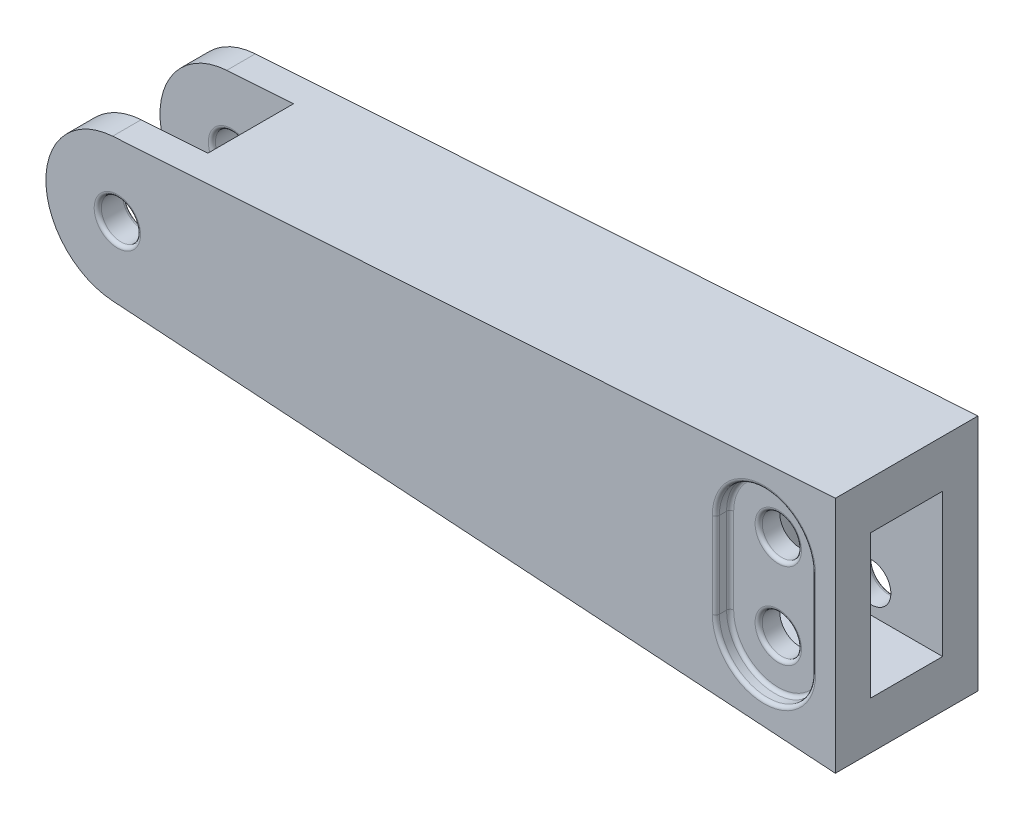
SolidWorks part; units mm, degrees
ref_plane "Front Plane" through (0, 0, 0) normal (0, 0, 1) x (1, 0, 0)
ref_plane "Top Plane" through (0, 0, 0) normal (0, 1, 0) x (1, 0, 0)
ref_plane "Right Plane" through (0, 0, 0) normal (1, 0, 0) x (0, 0, -1)
sketch "Sketch1" plane through (0, 0, 0) normal (0, 0, 1) x (1, 0, 0)
  line L0 (-50, 16.6955) -> (-151.3109, 10)
  line L1 (43.0973, 0) -> (50043.0973, 0) construction
  line L2 (0, 21.9801) -> (0, 50021.9801) construction
  line L3 (-50, -16.6955) -> (-151.3109, -10)
  line L4 (-50, 16.6955) -> (-50, -16.6955)
  line L5 (-50, 16.6955) -> (-50, -16.6955) construction
  line L6 (-6.5945, 19.5642) -> (-50, 16.6955) construction
  line L7 (-120.65, 205.549) -> (-120.65, -129.451) construction
  arc A0 (-151.3109, 10) -> (-151.3109, -10) centre (-150.65, 0) ccw
  point P9 (0, 0)
  dimension "D1" = 30
extrude "Boss-Extrude1" add sketch "Sketch1" along normal up to surface (20 mm away) contours L0 A0 L3 L4 region at (-99.4054, 0, 0)
sketch "Sketch2" plane through (-50, 0, 0) normal (1, 0, 0) x (0, 0, -1)
  line L1 (-4.965, -10.035) -> (-15.035, -10.035)
  line L2 (-4.965, -10.035) -> (-4.965, 10.035)
  line L3 (-4.965, 10.035) -> (-15.035, 10.035)
  line L4 (-20, 16.6955) -> (-20, -16.6955)
  line L5 (-20, -16.6955) -> (0, -16.6955)
  line L6 (0, -16.6955) -> (0, 16.6955)
  line L7 (0, 16.6955) -> (-20, 16.6955)
  line L8 (-20, 16.6955) -> (-20, -16.6955) construction
  line L9 (-20, -16.6955) -> (0, -16.6955) construction
  line L10 (0, -16.6955) -> (0, 16.6955) construction
  line L11 (0, 16.6955) -> (-20, 16.6955) construction
  line L12 (-15.035, -10.035) -> (-15.035, 10.035)
  line L13 (-4.965, -10.035) -> (-15.035, 10.035) construction
  line L14 (-4.965, 10.035) -> (-15.035, -10.035) construction
  point P2 (-10, 0)
  point P8 (-10, -16.6955)
  point P9 (-10, 0)
  dimension "D2" = 20.07
  dimension "D3" = 10.07
  dimension "D1" = 0
extrude "Cut-Extrude1" cut sketch "Sketch2" against normal blind 20
sketch "Sketch4" plane through (0, 0, 0) normal (0, 1, 0) x (1, 0, 0)
  line L0 (-160.6718, 0) -> (-160.6718, -20) construction
  line L1 (-160.6718, -4) -> (-141.95, -4)
  line L2 (-160.6718, -4) -> (-160.6718, -16)
  line L3 (-160.6718, -16) -> (-141.95, -16)
  line L4 (-141.95, -4) -> (-141.95, -16)
  line L5 (-160.6718, -4) -> (-141.95, -16) construction
  line L6 (-160.6718, -16) -> (-141.95, -4) construction
  line L7 (-160.6718, 0) -> (-160.6718, -20) construction
  line L8 (-151.3109, 0) -> (-160.6718, 0) construction
  line L9 (-151.3109, -20) -> (-151.3109, 0) construction
  point P4 (-151.3109, -10)
  point P12 (-160.6718, -10)
  point P17 (-151.3109, -4)
  dimension "D1" = 4
extrude "Cut-Extrude2" cut sketch "Sketch4" against normal through all both and the other way through all
sketch "Sketch5" plane through (0, 0, 0) normal (0, 0, -1) x (-1, 0, 0)
  circle A0 centre (150.65, 0) radius 2.75
  dimension "D1" = 5.5
extrude "Cut-Extrude3" cut sketch "Sketch5" against normal through all
sketch "Sketch6" plane through (0, 0, 0) normal (0, 0, -1) x (-1, 0, 0)
  line L0 (50, -16.6955) -> (50, 16.6955) construction
  line L1 (0, 0) -> (50000, 0) construction
  circle A0 centre (60, -6) radius 2.75
  circle A1 centre (60, 6) radius 2.75
  dimension "D1" = 5.5
  dimension "D2" = 10
  dimension "D3" = 6
extrude "Cut-Extrude4" cut sketch "Sketch6" against normal through all
sketch "Sketch8" plane through (0, 0, 0) normal (0, 0, -1) x (-1, 0, 0)
  line L0 (53.25, 6) -> (53.25, -6)
  line L2 (66.75, 6) -> (66.75, -6)
  circle A0 centre (60, -6) radius 2.75 construction
  circle A1 centre (60, 6) radius 2.75 construction
  circle A2 centre (60, -6) radius 2.75 construction
  circle A3 centre (60, 6) radius 2.75 construction
  arc A4 (53.25, -6) -> (66.75, -6) centre (60, -6) ccw
  arc A5 (66.75, 6) -> (53.25, 6) centre (60, 6) ccw
  circle A6 centre (60, 6) radius 6.75 construction
  circle A7 centre (60, -6) radius 6.75 construction
  point P7 (0, 0)
  point P16 (0, 0)
  dimension "D1" = 4
extrude "Cut-Extrude5" cut sketch "Sketch8" against normal blind 2
ref_plane "Plane1" through (0, 0, 10) normal (0, 0, -1) x (-1, 0, 0)
mirror "Mirror1" about plane through (0, 0, 10) normal (0, 0, -1) of "Cut-Extrude5"
fillet "Fillet2" radius 0.5 24 edges at (-60, -12.75, 2) (-53.25, 0, 2) (-60, 12.75, 2) (-60, -12.75, 0) (-53.25, 0, 0) (-60, 12.75, 0) (-60, -12.75, 18) (-53.25, 0, 18) (-60, 12.75, 18) (-60, -12.75, 20) (-53.25, 0, 20) (-60, 12.75, 20) (-153.4, 0, 4) (-153.4, 0, 0) (-147.9, 0, 16) (-153.4, 0, 20) (-57.25, -6, 18) (-57.25, 6, 18) (-62.75, -6, 2) (-62.75, 6, 2) (-66.75, 0, 18) (-66.75, 0, 20) (-66.75, 0, 2) (-66.75, 0, 0)
